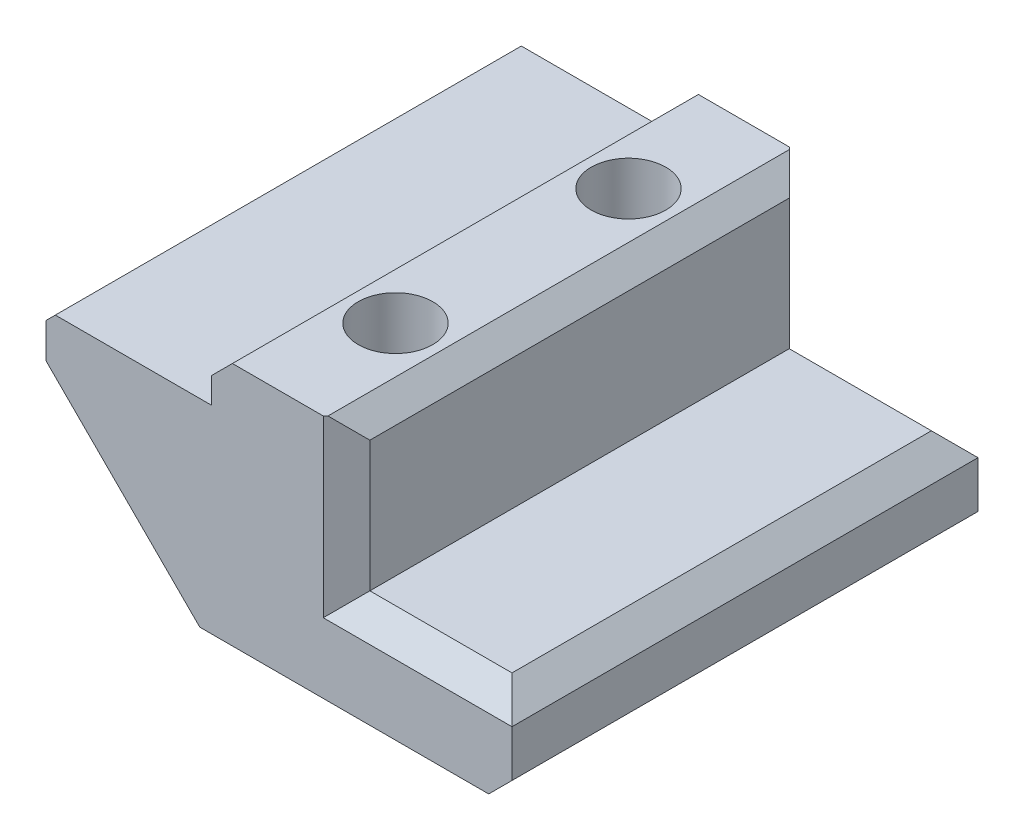
SolidWorks part; units mm, degrees
ref_plane "前视基准面" through (0, 0, 0) normal (0, 0, 1) x (1, 0, 0)
ref_plane "上视基准面" through (0, 0, 0) normal (0, 1, 0) x (1, 0, 0)
ref_plane "右视基准面" through (0, 0, 0) normal (1, 0, 0) x (0, 0, -1)
other "Configuration Table"
sketch "草图1" plane through (0, 0, 0) normal (0, 1, 0) x (1, 0, 0)
  line L1 (0, 0) -> (20, 0)
  line L2 (0, 0) -> (0, 20)
  line L3 (0, 20) -> (20, 20)
  line L4 (20, 0) -> (20, 20)
  dimension "D1" = 20
  dimension "D2" = 20
extrude "凸台-拉伸1" add sketch "草图1" along normal blind 4
sketch "草图2" plane through (0, 4, 0) normal (0, 1, 0) x (1, 0, 0)
  line L0 (0, 0) -> (20, 0) construction
  line L1 (0, 20) -> (12.9, 20)
  line L2 (0, 20) -> (0, 0)
  line L3 (0, 0) -> (12.9, 0)
  line L4 (12.9, 20) -> (12.9, 0)
  line L5 (20, 0) -> (20, 20) construction
  dimension "D1" = 7.1
extrude "凸台-拉伸2" add sketch "草图2" along normal blind 4.5
sketch "草图3" plane through (0, 0, 0) normal (0, -1, 0) x (-1, 0, 0)
  line L0 (0, 20) -> (0, 0) construction
  line L2 (0, 0) -> (-20, 0) construction
  circle A0 centre (-10, 5) radius 1.6
  circle A1 centre (-10, 15) radius 1.6
  dimension "D1" = 3.2
  dimension "D3" = 5
  dimension "D2" = 10
  dimension "D4" = 2
extrude "切除-拉伸1" cut sketch "草图3" against normal through all
sketch "草图4" plane through (0, 8.5, 0) normal (0, 1, 0) x (1, 0, 0)
  line L0 (12.9, 20) -> (0, 20) construction
  line L1 (7.1, 20) -> (12.9, 20)
  line L2 (7.1, 20) -> (7.1, 0)
  line L3 (7.1, 0) -> (12.9, 0)
  line L4 (12.9, 20) -> (12.9, 0)
  line L5 (0, 20) -> (0, 0) construction
  circle A0 centre (10, 15) radius 1.6
  circle A1 centre (10, 5) radius 1.6
  point P6 (10, 20)
  dimension "D1" = 5.8
  dimension "D2" = 10
extrude "凸台-拉伸3" add sketch "草图4" along normal blind 2
sketch "草图5" plane through (0, 0, 0) normal (0, -1, 0) x (-1, 0, 0)
  circle A0 centre (-10, 5) radius 3
  circle A1 centre (-10, 15) radius 3
  dimension "D1" = 6
  dimension "D2" = 6
extrude "切除-拉伸3" cut sketch "草图5" against normal blind 2.4
chamfer "倒角3" distance 1.5 angle 45 2 edges at (10, 2.4, -16.6) (10, 2.4, -6.6)
chamfer "倒角1" distance 6.6 angle 45 1 edges at (0, 0, -10)
chamfer "倒角2" distance 1 angle 45 6 edges at (20, 0, -10) (12.9, 7.25, -20) (16.45, 4, -20) (20, 4, -10) (16.45, 4, 0) (12.9, 7.25, 0)
chamfer "倒角4" distance 0.4 angle 45 1 edges at (0, 8.5, -10)
chamfer "倒角5" distance 0.9 angle 45 2 edges at (12.9, 10.5, -10) (7.1, 10.5, -10)
